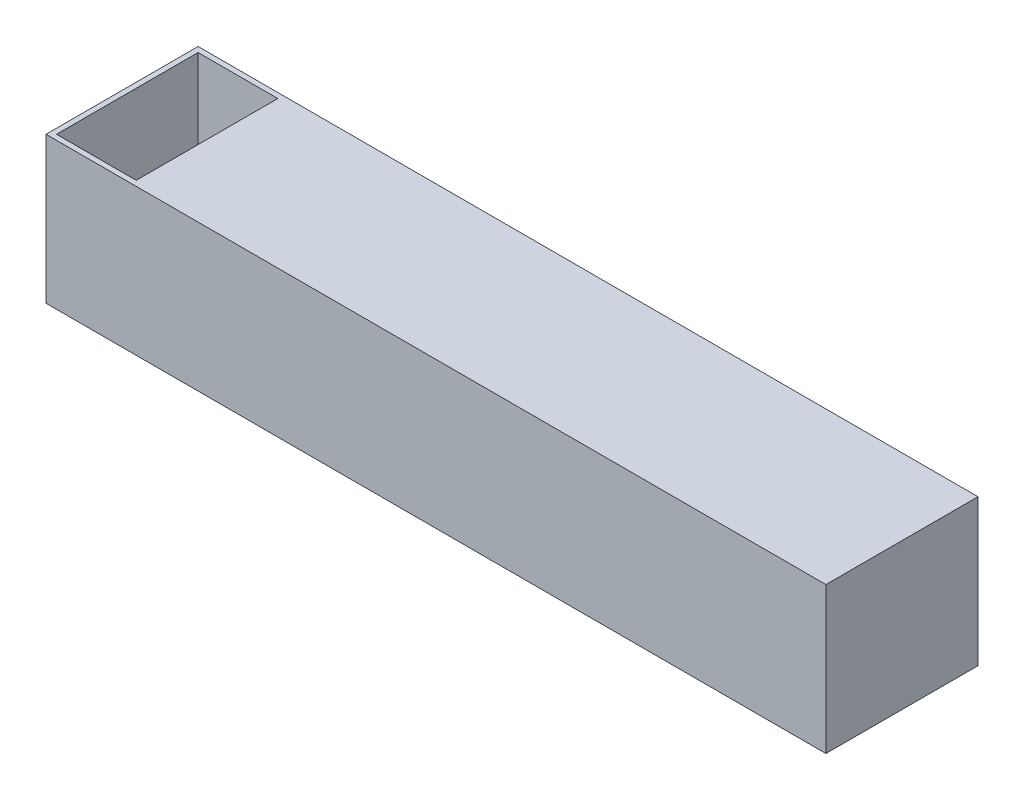
SolidWorks part; units mm, degrees
ref_plane "Plan de face" through (0, 0, 0) normal (0, 0, 1) x (1, 0, 0)
ref_plane "Plan de dessus" through (0, 0, 0) normal (0, 1, 0) x (1, 0, 0)
ref_plane "Plan de droite" through (0, 0, 0) normal (1, 0, 0) x (0, 0, -1)
sketch "Esquisse1" plane through (0, 0, 0) normal (0, 0, 1) x (1, 0, 0)
  line L0 (-31.5776, 126.5706) -> (625.9109, 69.0478)
  line L1 (-31.5776, 202.5706) -> (701.9109, 202.5706)
  line L2 (-31.5776, 202.5706) -> (-31.5776, 69.0478)
  line L3 (-31.5776, 69.0478) -> (701.9109, 69.0478)
  line L4 (701.9109, 202.5706) -> (701.9109, 69.0478)
  line L5 (-31.5776, 121.5515) -> (568.5424, 69.0478)
  line L7 (-36.5776, 205.5706) -> (706.9109, 205.5706)
  line L8 (-36.5776, 205.5706) -> (-36.5776, 66.0478)
  line L9 (-36.5776, 66.0478) -> (706.9109, 66.0478)
  line L10 (706.9109, 205.5706) -> (706.9109, 66.0478)
  dimension "D2" = 5
  dimension "D3" = 76
  dimension "D4" = 76
  dimension "D5" = 5
  dimension "D6" = 5
  dimension "D7" = 3
  dimension "D8" = 3
  dimension "D9" = 5
  dimension "D10" = 660
  dimension "D11" = 743.4885
  dimension "D12" = 139.5228
extrude "Boss.-Extru.1" add sketch "Esquisse1" along normal blind 135 contours L10 L7 L8 L9 L1 L4 L3 L2 | L2 L5 L3 L0 region at (283.0426, 96.5735, 0) region at (335.1667, 204.8141, 0)
extrude "Boss.-Extru.3" add sketch "Esquisse1<4>" against normal blind 5 contours L4 L1 L2 L0 L3 | L5 L2 L3 | L2 L5 L3 L0 | L10 L7 L8 L9 L1 L4 L3 L2 region at (370.4812, 147.1962, 0) region at (283.0426, 96.5735, 0) region at (168.4624, 86.549, 0) region at (335.1667, 204.8141, 0)
sketch "Esquisse1<4>" plane through (0, 0, 0) normal (0, 0, 1) x (1, 0, 0) same geometry as "Esquisse1"
sketch "Esquisse2" plane through (0, 0, 135) normal (0, 0, 1) x (1, 0, 0)
  line L1 (-36.5776, 205.5706) -> (706.9109, 205.5706)
  line L2 (-36.5776, 205.5706) -> (-36.5776, 66.0478)
  line L3 (-36.5776, 66.0478) -> (706.9109, 66.0478)
  line L4 (706.9109, 205.5706) -> (706.9109, 66.0478)
extrude "Boss.-Extru.4" add sketch "Esquisse2" along normal blind 5
sketch "Esquisse3" plane through (0, 205.5706, 0) normal (0, 1, 0) x (1, 0, 0)
  line L1 (-31.5776, 0) -> (44.4224, 0)
  line L2 (-31.5776, 0) -> (-31.5776, -135)
  line L3 (-31.5776, -135) -> (44.4224, -135)
  line L4 (44.4224, 0) -> (44.4224, -135)
  dimension "D4" = 135
  dimension "D5" = 76
extrude "Enlèv. mat.-Extru.1" cut sketch "Esquisse3" against normal blind 10
sketch "Esquisse4" plane through (0, 66.0478, 0) normal (0, -1, 0) x (1, 0, 0)
  line L1 (625.9109, 135) -> (701.9109, 135)
  line L2 (625.9109, 135) -> (625.9109, 0)
  line L3 (625.9109, 0) -> (701.9109, 0)
  line L4 (701.9109, 135) -> (701.9109, 0)
  dimension "D4" = 135
  dimension "D5" = 76
extrude "Enlèv. mat.-Extru.2" cut sketch "Esquisse4" against normal blind 10
